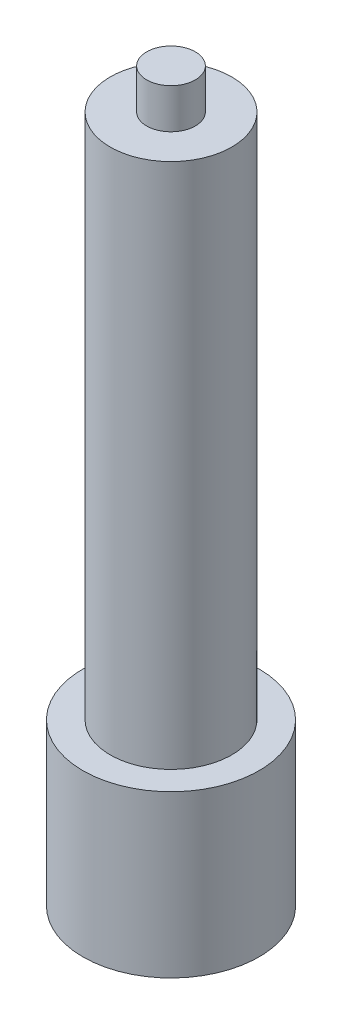
SolidWorks part; units mm, degrees
ref_plane "Front" through (0, 0, 0) normal (0, 0, 1) x (1, 0, 0)
ref_plane "Top" through (0, 0, 0) normal (0, 1, 0) x (1, 0, 0)
ref_plane "Right" through (0, 0, 0) normal (1, 0, 0) x (0, 0, -1)
sketch "Sketch2" plane through (0, 0, 0) normal (0, 0, 1) x (1, 0, 0)
  line L0 (0, 0) -> (0, 190)
  line L1 (0, -50) -> (0, 50) construction
  line L2 (0, 190) -> (6.35, 190)
  line L3 (6.35, 190) -> (6.35, 179.5681)
  line L4 (6.35, 179.5681) -> (15.875, 179.5681)
  line L5 (15.875, 179.5681) -> (15.875, 42.1206)
  line L6 (15.875, 42.1206) -> (23, 42.1206)
  line L7 (23, 42.1206) -> (23, 0)
  line L8 (50, 0) -> (-50, 0) construction
  line L9 (23, 0) -> (0, 0)
  dimension "D1" = 23
  dimension "D2" = 15.875
  dimension "D3" = 6.35
  dimension "D4" = 190
revolve "Revolve1" add sketch "Sketch2" angle 360 about L0
